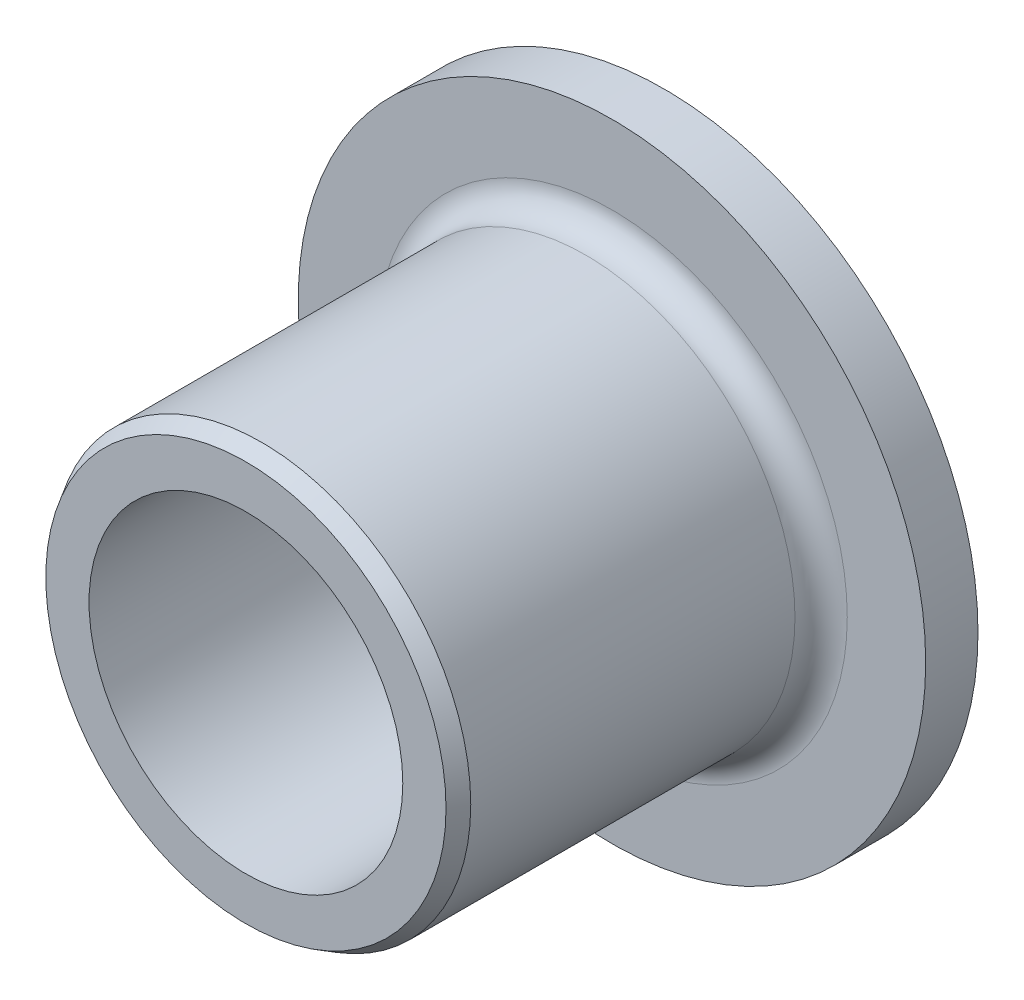
SolidWorks part; units mm, degrees
ref_plane "Front" through (0, 0, 0) normal (0, 0, 1) x (1, 0, 0)
ref_plane "Top" through (0, 0, 0) normal (0, 1, 0) x (1, 0, 0)
ref_plane "Right" through (0, 0, 0) normal (1, 0, 0) x (0, 0, -1)
ref_axis "side-side" through (80.9, 0, 0) along (-1, 0, 0)
ref_axis "up-down" through (0, 50, 0) along (0, -1, 0)
ref_axis "front-back" through (0, 0, -80.9) along (0, 0, 1)
sketch "Sketch1" plane through (0, 0, 0) normal (1, 0, 0) x (0, 0, -1)
  line L0 (0, 0) -> (9.2496, 0) construction
  line L3 (0, 6) -> (-1, 6)
  line L7 (-1.5, 4) -> (-7.7, 4)
  line L11 (-7.7, 4) -> (-8, 3.8268)
  line L16 (-8, 3.8268) -> (-8, 3)
  line L19 (0, 3) -> (-8, 3)
  line L24 (-1, 6) -> (-1, 4.5)
  line L27 (0, 3) -> (0, 6)
  arc A3 (-1.5, 4) -> (-1, 4.5) centre (-1.5, 4.5) ccw
  dimension "D1" = 1
revolve "Revolve1" add sketch "Sketch1" angle 360 about L0
